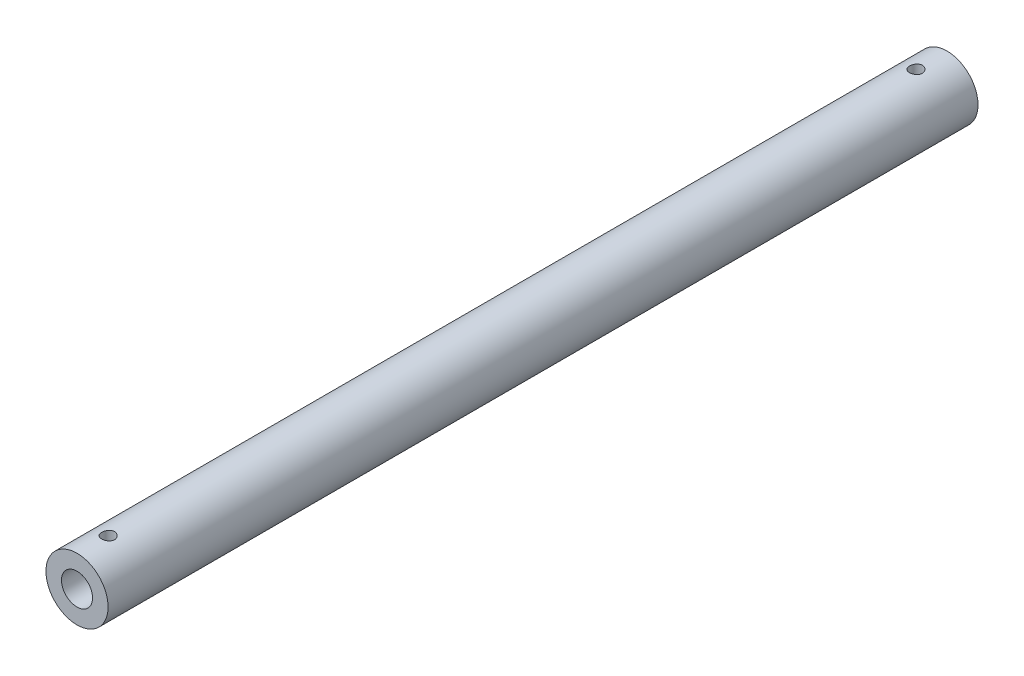
SolidWorks part; units mm, degrees
ref_plane "Front Plane" through (0, 0, 0) normal (0, 0, 1) x (1, 0, 0)
ref_plane "Top Plane" through (0, 0, 0) normal (0, 1, 0) x (1, 0, 0)
ref_plane "Right Plane" through (0, 0, 0) normal (1, 0, 0) x (0, 0, -1)
sketch "Sketch1" plane through (0, 0, 0) normal (0, 0, 1) x (1, 0, 0)
  circle A0 centre (0, 0) radius 15
  circle A1 centre (0, 0) radius 7.5
  dimension "D1" = 30
  dimension "D2" = 7.5
extrude "Boss-Extrude1" add sketch "Sketch1" along normal blind 210 and the other way blind 210
sketch "Sketch3" plane through (0, 0, 0) normal (0, 1, 0) x (1, 0, 0)
  line L0 (0, 0) -> (0, 210) construction
  line L1 (7.5, 210) -> (-7.5, 210) construction
  circle A0 centre (0, 195) radius 3.1
  dimension "D1" = 6.2
  dimension "D2" = 15
extrude "Cut-Extrude1" cut sketch "Sketch3" along normal blind 30
mirror "Mirror1" about plane through (0, 0, 0) normal (0, 0, 1) of "Cut-Extrude1"
